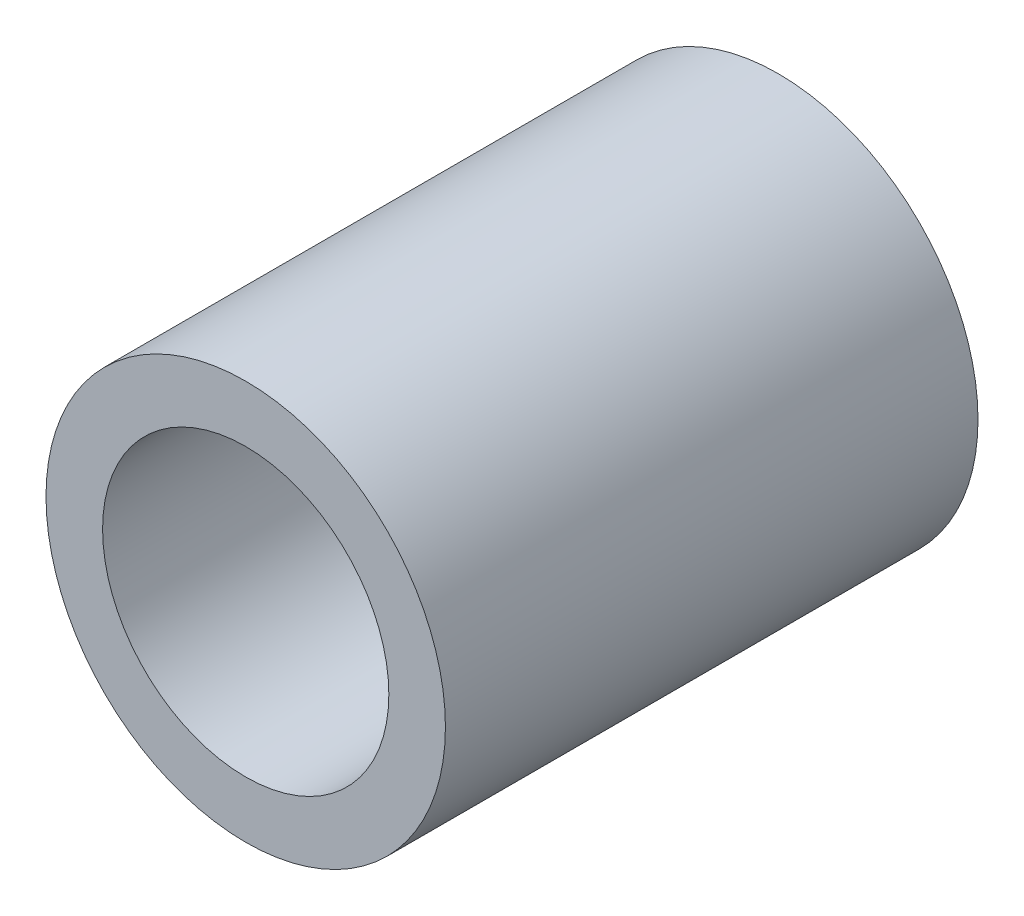
SolidWorks part; units mm, degrees
material "Nylon 101"
ref_plane "Front Plane" through (0, 0, 0) normal (0, 0, 1) x (1, 0, 0)
ref_plane "Top Plane" through (0, 0, 0) normal (0, 1, 0) x (1, 0, 0)
ref_plane "Right Plane" through (0, 0, 0) normal (1, 0, 0) x (0, 0, -1)
sketch "Sketch1" plane through (0, 0, 0) normal (0, 0, 1) x (1, 0, 0)
  circle A0 centre (0, 0) radius 3
  circle A1 centre (0, 0) radius 2.15
  dimension "OD" = 6
  dimension "ID" = 4.3
extrude "Extrude1" add sketch "Sketch1" along normal mid plane 8
sketch "Sketch2" plane through (0, 0, 0) normal (1, 0, 0) x (0, 0, -1)
  line L0 (-4, -2.15) -> (4, -2.15) construction
  line L3 (4, 2.15) -> (-4, 2.15) construction
  line L5 (-4, -2.15) -> (4, -2.15)
  line L6 (4, 2.15) -> (-4, 2.15)
sketch "Sketch4" plane through (0, 0, 4) normal (0, 0, 1) x (1, 0, 0)
  line L0 (0, 0) -> (-1.5203, 1.5203)
  line L1 (0, -1.65) -> (0, 1.65) construction
  circle A0 centre (0, 0) radius 2.15 construction
  dimension "D1" = 45
